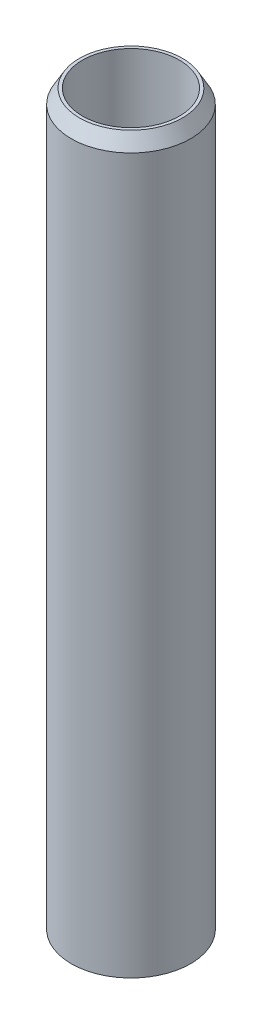
SolidWorks part; units mm, degrees
ref_plane "Front Plane" through (0, 0, 0) normal (0, 0, 1) x (1, 0, 0)
ref_plane "Top Plane" through (0, 0, 0) normal (0, 1, 0) x (1, 0, 0)
ref_plane "Right Plane" through (0, 0, 0) normal (1, 0, 0) x (0, 0, -1)
sketch "Sketch1" plane through (0, 0, 0) normal (0, 1, 0) x (1, 0, 0)
  circle A0 centre (0, 0) radius 25
  dimension "SHAFT_OD" = 50
extrude "Boss-Extrude1" add sketch "Sketch1" along normal blind 308.6004
sketch "Sketch2" plane through (0, 0, 0) normal (0, 1, 0) x (1, 0, 0)
  circle A0 centre (0, 0) radius 20.3291
  dimension "BORE_D" = 40.6582
extrude "Cut-Extrude1" cut sketch "Sketch2" along normal through all
chamfer "Chamfer1" distance 5.872 angle 30 2 edges at (0, 308.6004, 25) (0, 0, 25) first distance on face at (0, 308.6004, 25) first distance on face at (0, 0, 20.3291)
